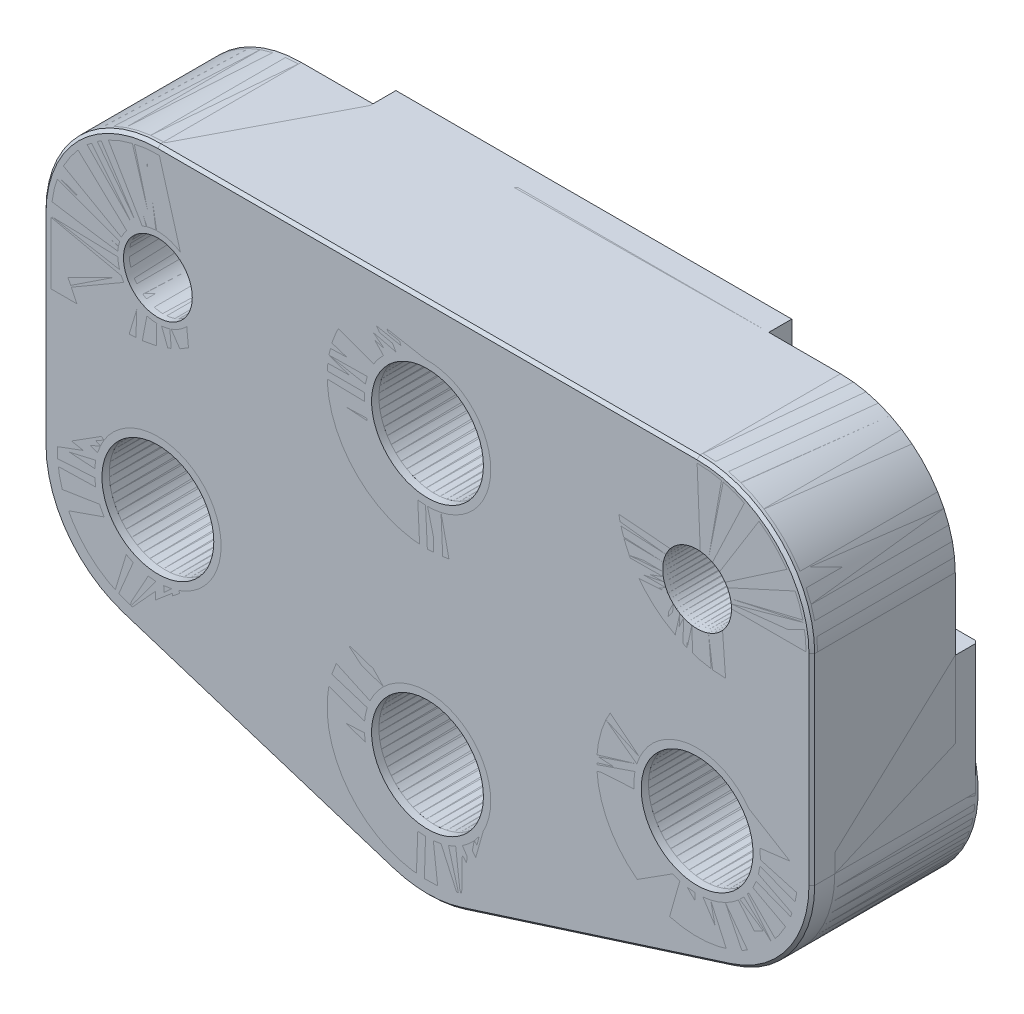
SolidWorks part; units mm, degrees
material "AISI 1020"
ref_plane "Plano superior" through (0, 0, 0) normal (0, 0, 1) x (1, 0, 0)
ref_plane "Plano frontal" through (0, 0, 0) normal (0, 1, 0) x (1, 0, 0)
ref_plane "Plano direito" through (0, 0, 0) normal (1, 0, 0) x (0, 0, -1)
sketch "Esboço1" plane through (0, 0, 0) normal (0, 0, 1) x (1, 0, 0)
  line L0 (-53.0808, -54.0532) -> (-6.0808, -69.0532)
  line L1 (53.0808, -54.0532) -> (6.0808, -69.0532)
  line L2 (-67, -35) -> (-67, 20)
  line L3 (-67, 20) -> (67, 20)
  line L4 (67, 20) -> (67, -35)
  arc A0 (-6.0808, -69.0532) -> (6.0808, -69.0532) centre (0, -50) ccw
  arc A1 (53.0808, -54.0532) -> (67, -35) centre (47, -35) ccw
  arc A2 (-67, -35) -> (-53.0808, -54.0532) centre (-47, -35) ccw
  dimension "D1" = 50
  dimension "D2" = 40
  dimension "D3" = 40
  dimension "D6" = 40
  dimension "D4" = 35
  dimension "D5" = 47
  dimension "D7" = 47
  dimension "D8" = 134
  dimension "D9" = 20
extrude "Ressalto-extrusão1" add sketch "Esboço1" along normal blind 22
sketch "Esboço3" plane through (0, 0, 22) normal (0, 0, 1) x (1, 0, 0)
  line L1 (-67, 20) -> (-32, 20)
  line L2 (-67, 20) -> (-67, -12)
  line L3 (-67, -12) -> (-32, -12)
  line L4 (-32, 20) -> (-32, -12)
  line L5 (67, 20) -> (32, 20)
  line L6 (67, 20) -> (67, -12)
  line L7 (67, -12) -> (32, -12)
  line L8 (32, 20) -> (32, -12)
  dimension "D1" = 35
  dimension "D2" = 32
  dimension "D3" = 35
  dimension "D4" = 32
extrude "Ressalto-extrusão2" add sketch "Esboço3" along normal blind 3
sketch "Esboço4" plane through (0, 0, 22) normal (0, 0, 1) x (1, 0, 0)
  circle A0 centre (0, 0) radius 17.5
  circle A1 centre (-47, -35) radius 17.5
  circle A2 centre (0, -50) radius 17.5
  circle A3 centre (47, -35) radius 17.5
  dimension "D1" = 35
extrude "Ressalto-extrusão3" add sketch "Esboço4" along normal blind 3
fillet "Filete2" radius 20 2 edges at (-67, 20, 12.5) (67, 20, 12.5)
fillet "Filete3" radius 20 2 edges at (32, -12, 23.5) (-32, -12, 23.5)
chamfer "Chanfro2" distance 1 angle 45 6 edges at (-39.5, 20, 25) (-67, -6, 25) (-61.1421, 14.1421, 25) (67, -6, 25) (61.1421, 14.1421, 25) (39.5, 20, 25)
hole_wizard "Furo roscado de M221" positions "Esboço5" profile "Esboço6" tap size "M22" standard "DIN" end condition through all
sketch "Esboço5" plane through (0, 0, 25) normal (0, 0, 1) x (1, 0, 0)
  point P0 (0, 0)
  point P3 (-47, -35)
  point P6 (0, -50)
  point P9 (47, -35)
sketch "Esboço6" plane through (0, 0, 25) normal (1, 0, 0) x (0, -1, 0)
  line L0 (0, 0) -> (0, 25)
  line L1 (0, 25) -> (9.75, 25)
  line L2 (9.75, 25) -> (9.75, 0)
  line L5 (9.75, 0) -> (0, 0)
  line L11 (0, -6.35) -> (0, 107.95) construction
  dimension "Thru Tap Drill Dia." = 19.5
  dimension "Thru Tap Drill Depth" = 25
cosmetic thread "Rosca de furo1" parameters "D2"=22
cosmetic thread "Rosca de furo2" parameters "D2"=22
cosmetic thread "Rosca de furo3" parameters "D2"=22
cosmetic thread "Rosca de furo4" parameters "D2"=22
hole_wizard "Furos-guia com Ø12.0mm1" positions "Esboço12" profile "Esboço13" hole size "Ø12.0" standard "DIN" end condition through all
sketch "Esboço12" plane through (0, 0, 25) normal (0, 0, 1) x (1, 0, 0)
  point P0 (-47, 0)
  point P3 (47, 0)
sketch "Esboço13" plane through (-47, 0, 25) normal (1, 0, 0) x (0, -1, 0)
  line L0 (0, 0) -> (0, 25)
  line L1 (0, 25) -> (6, 25)
  line L2 (6, 25) -> (6, 0)
  line L5 (6, 0) -> (0, 0)
  line L11 (0, -6.35) -> (0, 107.95) construction
  dimension "Thru Hole Dia." = 12
  dimension "Thru Hole Depth" = 25
chamfer "Chanfro3" distance 1 angle 45 2 edges at (53, 0, 0) (-41, 0, 0)
sketch "Esboço14" plane through (0, 0, 0) normal (0, 0, -1) x (-1, 0, 0)
  circle A0 centre (0, 0) radius 9.75
  circle A1 centre (47, -35) radius 9.75
  circle A2 centre (0, -50) radius 9.75
  circle A3 centre (-47, -35) radius 9.75
  circle A4 centre (-47, -35) radius 20
  circle A5 centre (0, 0) radius 20
  circle A7 centre (47, -35) radius 20
  circle A8 centre (0, -50) radius 20
  dimension "D1" = 19.5
  dimension "D2" = 40
extrude "Ressalto-extrusão4" add sketch "Esboço14" along normal blind 4
fillet "Filete4" radius 2 4 edges at (30.8504, -23.202, 0) (0, -30, 0) (-20, 0, 0) (-30.8504, -23.202, 0)
fillet "Filete18" radius 1 8 edges at (-67, -23.5, 22) (-63.1496, -46.798, 22) (-29.5808, -61.5532, 22) (0, -70, 22) (67, -23.5, 22) (63.1496, -46.798, 22) (29.5808, -61.5532, 22) (0, 20, 22)
fillet "Filete19" radius 1 10 edges at (32, 13.5, 25) (59, -12, 25) (-37.8579, -6.1421, 25) (-59, -12, 25) (-66, -6, 25) (-60.435, 13.435, 25) (-39.5, 19, 25) (-32, 13.5, 25) (-41, 0, 25) (37.8579, -6.1421, 25)
fillet "Filete20" radius 1 4 edges at (-29.5, -35, 22) (17.5, -50, 22) (17.5, 0, 22) (64.5, -35, 22)
sketch "Esboço15" plane through (0, 0, 0) normal (0, 0, 1) x (1, 0, 0)
  line L2 (53.0808, -54.0532) -> (6.0808, -69.0532)
  line L3 (-6.0808, -69.0532) -> (-53.0808, -54.0532)
  line L7 (67, 0) -> (67, -35)
  line L8 (-47, 20) -> (47, 20)
  line L9 (-67, -35) -> (-67, 0)
  arc A1 (-6.0808, -69.0532) -> (6.0808, -69.0532) centre (0, -50) ccw
  arc A4 (53.0808, -54.0532) -> (67, -35) centre (47, -35) ccw
  arc A5 (-67, -35) -> (-53.0808, -54.0532) centre (-47, -35) ccw
  arc A8 (-47, 20) -> (-67, 0) centre (-47, 0) ccw
  arc A9 (67, 0) -> (47, 20) centre (47, 0) ccw
extrude "Ressalto-extrusão5" add sketch "Esboço15" along normal blind 25 and the other way blind 4 separate body
sketch "Esboço16" plane through (0, 0, 25) normal (0, 0, 1) x (1, 0, 0)
  circle A6 centre (47, 0) radius 6
  circle A7 centre (0, 0) radius 9.75
  circle A8 centre (47, -35) radius 9.75
  circle A9 centre (0, -50) radius 9.75
  circle A10 centre (-47, -35) radius 9.75
  circle A11 centre (-47, 0) radius 6
hole_wizard "Furo roscado de M222" positions "Esboço17" profile "Esboço18" tap size "M22" standard "DIN" end condition through all
sketch "Esboço17" plane through (0, 0, 25) normal (0, 0, 1) x (1, 0, 0)
  point P0 (-47, -35)
  point P3 (0, -50)
  point P6 (0, 0)
  point P9 (47, -35)
sketch "Esboço18" plane through (-47, -35, 25) normal (1, 0, 0) x (0, -1, 0)
  line L0 (0, 0) -> (0, 29)
  line L1 (0, 29) -> (9.75, 29)
  line L2 (9.75, 29) -> (9.75, 1.275)
  line L3 (9.75, 1.275) -> (11.025, 0)
  line L5 (11.025, 0) -> (0, 0)
  line L6 (-9.75, 1.275) -> (-11.025, 0) construction
  line L11 (0, -6.35) -> (0, 107.95) construction
  dimension "Thru Tap Drill Dia." = 19.5
  dimension "Thru Tap Drill Depth" = 29
  dimension "Near C'Sink Dia." = 22.05
  dimension "Near C'Sink Angle" = 90
cosmetic thread "Rosca de furo5" parameters "D2"=22
cosmetic thread "Rosca de furo6" parameters "D2"=22
cosmetic thread "Rosca de furo7" parameters "D2"=22
cosmetic thread "Rosca de furo8" parameters "D2"=22
sketch "Esboço19" plane through (0, 0, 25) normal (0, 0, 1) x (1, 0, 0)
  circle A0 centre (47, 0) radius 6 construction
  circle A1 centre (-47, 0) radius 6 construction
  circle A2 centre (47, 0) radius 6
  circle A3 centre (-47, 0) radius 6
extrude "Corte-extrusão1" cut sketch "Esboço19" against normal blind 59
sketch "Esboço20" plane through (0, 0, -4) normal (0, 0, -1) x (-1, 0, 0)
  line L0 (-34.5, 0) -> (-34.5, 37.9928)
  line L1 (-34.5, 37.9928) -> (-80.0367, 37.9928)
  line L2 (-80.0367, 37.9928) -> (-80.0367, -12.5)
  line L3 (-80.0367, -12.5) -> (-47, -12.5)
  line L4 (0, 0) -> (0, 37.9928) construction
  line L9 (80.0367, -12.5) -> (47, -12.5)
  line L10 (80.0367, 37.9928) -> (80.0367, -12.5)
  line L11 (34.5, 37.9928) -> (80.0367, 37.9928)
  line L12 (34.5, 0) -> (34.5, 37.9928)
  arc A0 (-47, -12.5) -> (-34.5, 0) centre (-47, 0) ccw
  arc A3 (47, -12.5) -> (34.5, 0) centre (47, 0) cw
  dimension "D1" = 25
extrude "Corte-extrusão2" cut sketch "Esboço20" against normal blind 4
chamfer "Chanfro4" distance 0.5 angle 45 21 edges at (-67, -12.5, -2) (-67, -6.25, 0) (-40.75, 20, 0) (-61.1421, 14.1421, 0) (67, -23.75, -4) (63.1496, -46.798, -4) (-67, -23.75, -4) (29.5808, -61.5532, -4) (-63.1496, -46.798, -4) (0, -70, -4) (-29.5808, -61.5532, -4) (61.1421, 14.1421, 25) (0, 20, 25) (67, -17.5, 25) (-61.1421, 14.1421, 25) (63.1496, -46.798, 25) (-67, -17.5, 25) (29.5808, -61.5532, 25) (-63.1496, -46.798, 25) (0, -70, 25) (-29.5808, -61.5532, 25)
